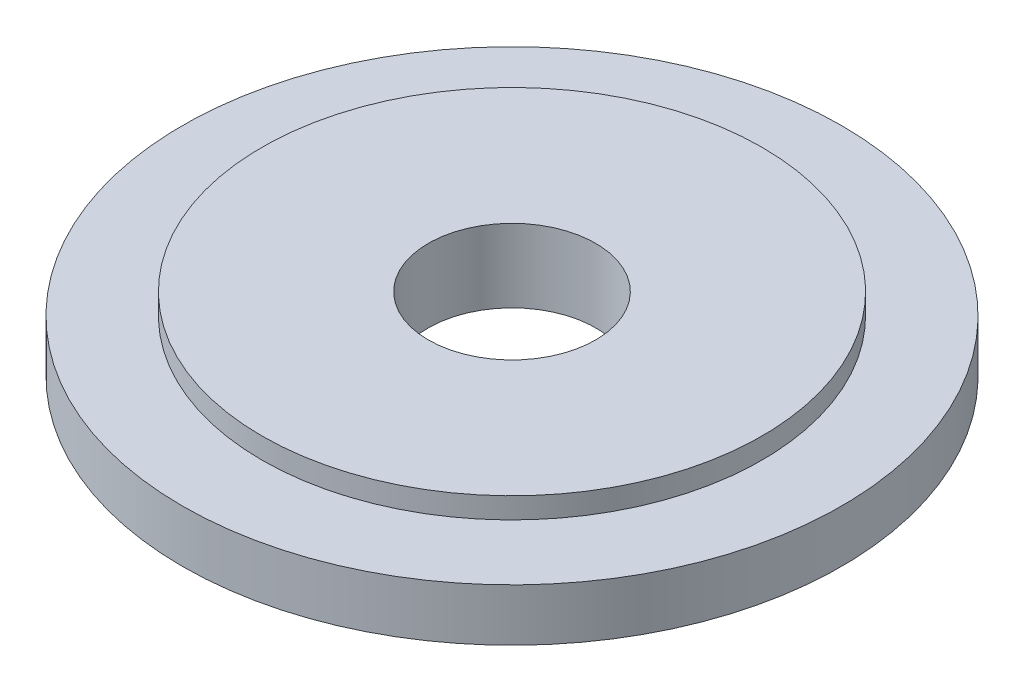
SolidWorks part; units mm, degrees
ref_plane "Front Plane" through (0, 0, 0) normal (0, 0, 1) x (1, 0, 0)
ref_plane "Top Plane" through (0, 0, 0) normal (0, 1, 0) x (1, 0, 0)
ref_plane "Right Plane" through (0, 0, 0) normal (1, 0, 0) x (0, 0, -1)
sketch "Croquis1" plane through (0, 0, 0) normal (0, 1, 0) x (1, 0, 0)
  circle A0 centre (0, 0) radius 23.9
  circle A1 centre (0, 0) radius 31.5
  circle A2 centre (0, 0) radius 8
  dimension "D1" = 47.8
  dimension "D2" = 63
  dimension "D3" = 16
extrude "Saliente-Extruir1" add sketch "Croquis1" along normal blind 2 contours A0 A2 region at (-23.224, 0, 0)
extrude "Saliente-Extruir2" add sketch "Croquis1<3>" against normal blind 5 contours A1 A0 | A0 A2 region at (-23.224, 0, 0) region at (-30.609, 0, 0)
sketch "Croquis1<3>" plane through (0, 0, 0) normal (0, 1, 0) x (1, 0, 0) same geometry as "Croquis1"
equation "\"ID\"= 47.8"
equation "\"D1@Croquis1\"=\"ID\""
equation "\"OD\"= 63"
equation "\"D2@Croquis1\"=\"OD\""
equation "\"Dmandril\" = 16"
equation "\"D3@Croquis1\"=\"Dmandril\""
